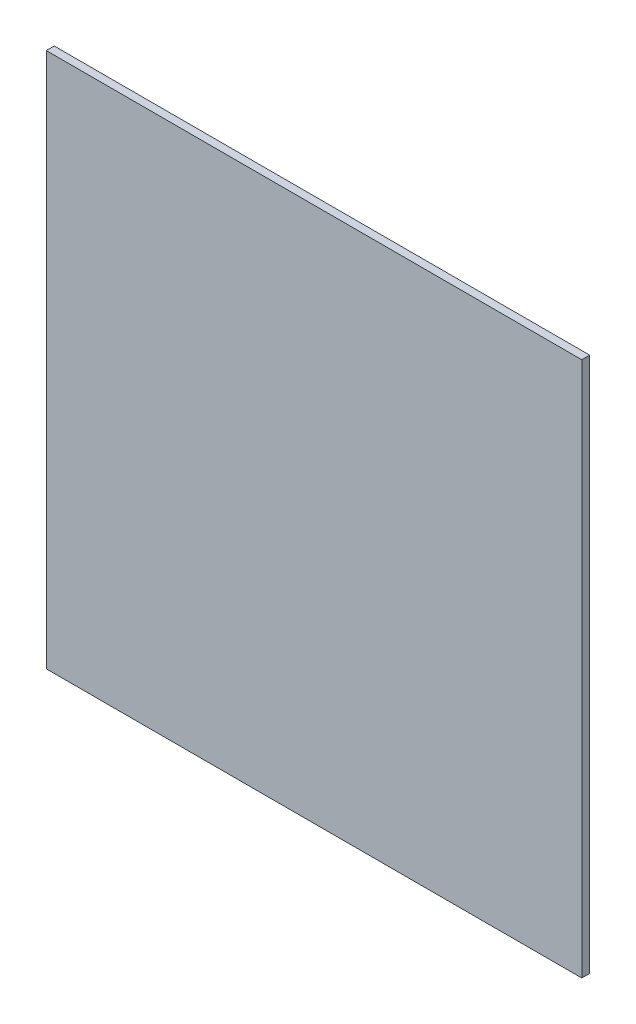
SolidWorks part; units mm, degrees
material "Glas"
ref_plane "Ebene vorne" through (0, 0, 0) normal (0, 0, 1) x (1, 0, 0)
ref_plane "Ebene oben" through (0, 0, 0) normal (0, 1, 0) x (1, 0, 0)
ref_plane "Ebene rechts" through (0, 0, 0) normal (1, 0, 0) x (0, 0, -1)
sketch "Skizze1" plane through (0, 0, 0) normal (0, 0, 1) x (1, 0, 0)
  line L1 (-67.5, -67.5) -> (67.5, -67.5)
  line L2 (-67.5, -67.5) -> (-67.5, 67.5)
  line L3 (-67.5, 67.5) -> (67.5, 67.5)
  line L4 (67.5, -67.5) -> (67.5, 67.5)
  line L5 (-67.5, -67.5) -> (67.5, 67.5) construction
  line L6 (-67.5, 67.5) -> (67.5, -67.5) construction
  point P0 (0, 0)
  dimension "D1" = 135
  dimension "D2" = 135
extrude "Aufsatz-Linear austragen1" add sketch "Skizze1" against normal blind 2
